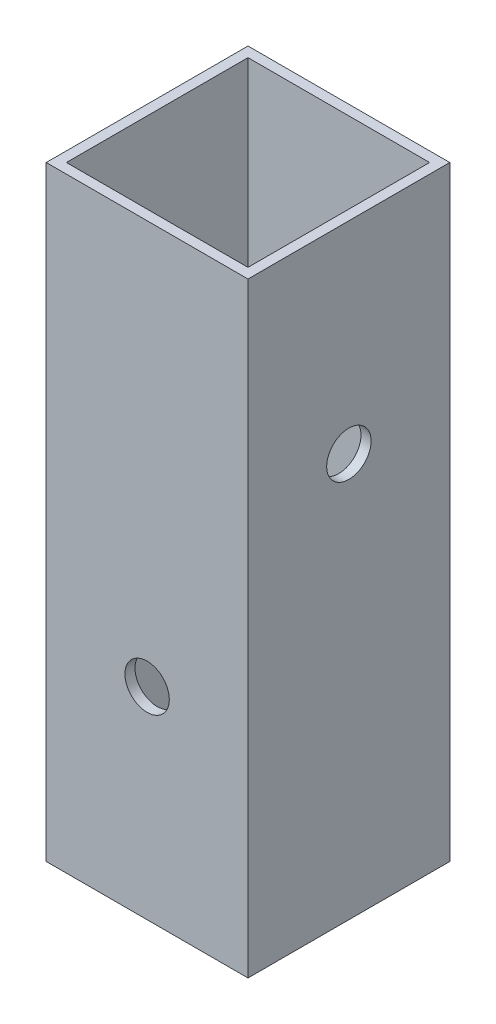
SolidWorks part; units mm, degrees
ref_plane "前视基准面" through (0, 0, 0) normal (0, 0, 1) x (1, 0, 0)
ref_plane "上视基准面" through (0, 0, 0) normal (0, 1, 0) x (1, 0, 0)
ref_plane "右视基准面" through (0, 0, 0) normal (1, 0, 0) x (0, 0, -1)
sketch "草图1" plane through (0, 0, 0) normal (0, 1, 0) x (1, 0, 0)
  line L2 (10, 0) -> (10, 10)
  line L3 (0, 10) -> (10, 10)
  line L6 (9, 0) -> (9, 9)
  line L7 (0, 9) -> (9, 9)
  line L8 (0, -10) -> (10, -10)
  line L9 (10, 0) -> (10, -10)
  line L10 (0, -9) -> (9, -9)
  line L11 (9, 0) -> (9, -9)
  line L12 (-10, 0) -> (-10, -10)
  line L13 (0, -10) -> (-10, -10)
  line L14 (-9, 0) -> (-9, -9)
  line L15 (0, -9) -> (-9, -9)
  line L16 (0, 10) -> (-10, 10)
  line L17 (-10, 0) -> (-10, 10)
  line L18 (0, 9) -> (-9, 9)
  line L19 (-9, 0) -> (-9, 9)
  point P27 (0, 0)
extrude "凸台-拉伸1" add sketch "草图1" against normal blind 280
sketch "草图2" plane through (0, 0, 10) normal (0, 0, 1) x (1, 0, 0)
  circle A0 centre (0, -40) radius 2.2
  circle A1 centre (0, -80) radius 2.2
  circle A2 centre (0, -120) radius 2.2
  circle A3 centre (0, -180) radius 2.2
  circle A4 centre (0, -220) radius 2.2
  circle A5 centre (0, -260) radius 2.2
  dimension "D1" = 3
  dimension "D2" = 2
  dimension "D3" = 3
extrude "切除-拉伸1" cut sketch "草图2" against normal blind 280
sketch "草图3" plane through (10, 0, 0) normal (1, 0, 0) x (0, 0, -1)
  circle A0 centre (0, -60) radius 2.2
  circle A1 centre (0, -100) radius 2.2
  circle A2 centre (0, -150) radius 2.2
  circle A3 centre (0, -200) radius 2.2
  circle A4 centre (0, -240) radius 2.2
extrude "切除-拉伸2" cut sketch "草图3" against normal blind 20
sketch "草图4" plane through (0, 0, 10) normal (0, 0, 1) x (1, 0, 0)
  line L0 (0, -220) -> (10, -220)
  line L1 (10, -280) -> (10, 0) construction
  line L2 (10, -220) -> (10, 0)
  line L3 (10, 0) -> (-10, 0)
  line L4 (-10, 0) -> (-10, -220)
  line L5 (-10, -280) -> (-10, 0) construction
  line L6 (-10, -220) -> (0, -220)
extrude "切除-拉伸3" cut sketch "草图4" against normal blind 59
sketch "草图5" plane through (0, 0, 10) normal (0, 0, 1) x (1, 0, 0)
  line L0 (-2.2, -220) -> (2.2, -220)
  arc A0 (-2.2, -220) -> (2.2, -220) centre (0, -220) ccw
extrude "凸台-拉伸3" add sketch "草图5" against normal blind 20
sketch "草图6" plane through (0, -220, 0) normal (0, 1, 0) x (1, 0, 0)
  line L0 (-2.2, 9) -> (2.2, 9)
  line L1 (-2.2, 9) -> (-2.2, -9.0035)
  line L2 (2.2, 9) -> (2.2, -9.0035)
  line L3 (-2.2, -9.0035) -> (2.2, -9.0035)
extrude "切除-拉伸4" cut sketch "草图6" against normal blind 20
